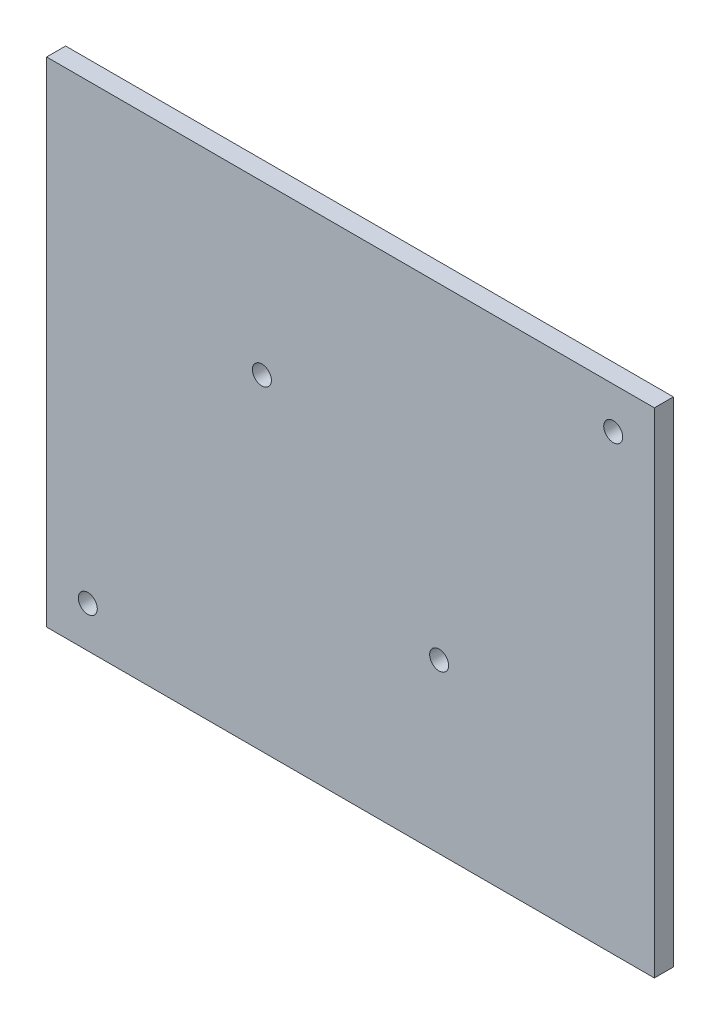
SolidWorks part; units mm, degrees
ref_plane "Alzado" through (0, 0, 0) normal (0, 0, 1) x (1, 0, 0)
ref_plane "Planta" through (0, 0, 0) normal (0, 1, 0) x (1, 0, 0)
ref_plane "Vista lateral" through (0, 0, 0) normal (1, 0, 0) x (0, 0, -1)
sketch "Croquis1" plane through (0, 0, 0) normal (0, 0, 1) x (1, 0, 0)
  line L5 (-48, -39) -> (48, -39)
  line L6 (-48, -39) -> (-48, 39)
  line L19 (-48, 39) -> (48, 39)
  line L24 (48, -39) -> (48, 39)
  line L25 (-48, -39) -> (48, 39) construction
  line L26 (-48, 39) -> (48, -39) construction
  point P0 (0, 0)
  dimension "D1" = 96
  dimension "D2" = 78
extrude "Saliente-Extruir2" add sketch "Croquis1" against normal blind 3 contours L5 region at (0, 0, 0)
sketch "Croquis2" plane through (0, 0, 0) normal (0, 0, 1) x (1, 0, 0)
  line L0 (0, 39) -> (0, -39) construction
  line L1 (-21.5, 20) -> (21.5, 20) construction
  line L2 (-21.5, 20) -> (-21.5, -20) construction
  line L3 (-21.5, -20) -> (21.5, -20) construction
  line L4 (21.5, 20) -> (21.5, -20) construction
  line L5 (-48, 39) -> (48, 39) construction
  line L6 (0, 20) -> (0, -20) construction
  line L15 (-21.5, 0) -> (21.5, 0) construction
  line L16 (-48, -39) -> (48, -39) construction
  line L17 (-48, 0) -> (48, 0) construction
  line L18 (-48, -39) -> (-48, 39) construction
  line L20 (-48, 39) -> (48, 39)
  line L21 (48, -39) -> (48, 39) construction
  line L22 (-48, 39) -> (-48, -39)
  line L23 (-48, -39) -> (48, -39)
  line L24 (48, 39) -> (48, -39)
  circle A1 centre (-14, 12.5) radius 1.5
  circle A2 centre (14, -12.5) radius 1.5
  circle A3 centre (-41.5, -32.5) radius 1.5 construction
  circle A4 centre (41.5, 32.5) radius 1.5 construction
  circle A5 centre (-41.5, -32.5) radius 1.5
  circle A6 centre (41.5, 32.5) radius 1.5
  point P8 (0, 0)
  dimension "D1" = 7.5
  dimension "D2" = 7.5
  dimension "D3" = 7.5
  dimension "D4" = 3
  dimension "D7" = 3
  dimension "D5" = 43
  dimension "D6" = 40
  dimension "D9" = 7.5
extrude "Cortar-Extruir1" cut sketch "Croquis2" against normal through all flip side to cut
sketch "Sketch6" plane through (0, 0, 0) normal (0, 0, 1) x (1, 0, 0)
  line L0 (1.7275, -9.1526) -> (1.7275, -16.0516)
  line L1 (2.8268, -16.0516) -> (2.8268, -9.1526)
  line L2 (2.2798, -8.9746) -> (2.2801, -8.9746)
  line L3 (-11.373, -9.3975) -> (-11.373, -16.0515)
  line L4 (-10.2742, -16.0515) -> (-10.2742, -12.9911)
  line L5 (-10.2742, -12.9911) -> (-9.54, -12.9911)
  line L6 (-7.8119, -14.3075) -> (-7.0556, -15.9986)
  line L7 (-6.0064, -15.6431) -> (-6.7462, -14.0625)
  line L8 (-9.2084, -9.0081) -> (-10.9645, -9.0083)
  line L9 (-4.2786, -9.3975) -> (-4.2786, -16.0515)
  line L10 (-3.1793, -16.0515) -> (-3.1793, -13.0584)
  line L11 (-3.1793, -13.0584) -> (-0.3195, -13.0584)
  line L12 (-0.3195, -12.2597) -> (-3.1793, -12.2597)
  line L13 (-3.1793, -12.2597) -> (-3.1793, -9.8191)
  line L14 (-3.1793, -9.8191) -> (-0.1539, -9.8191)
  line L15 (-0.1539, -9.0062) -> (-3.8702, -9.0083)
  line L16 (5.024, -9.3975) -> (5.024, -15.8065)
  line L17 (5.4325, -16.1957) -> (7.1771, -16.1957)
  line L18 (7.2987, -9.0086) -> (5.4325, -9.0083)
  line L19 (-10.2744, -9.7961) -> (-9.3524, -9.7961)
  line L20 (-9.2031, -12.2181) -> (-10.2742, -12.2181)
  line L21 (-10.2742, -12.2181) -> (-10.2744, -9.7961)
  line L22 (6.1171, -9.8011) -> (7.2378, -9.8011)
  line L23 (7.2489, -15.3934) -> (6.1171, -15.3934)
  line L24 (6.1171, -15.3934) -> (6.1171, -9.8011)
  line L25 (-11.5, -6.9036) -> (-11.5, 9.9857)
  line L26 (-11.5, 9.9857) -> (-5.3069, 16.2)
  line L27 (-5.3069, 16.2) -> (11.5, 16.2)
  line L28 (11.5, 16.2) -> (11.5, -7.0088)
  line L29 (11.5, -7.0088) -> (10.3931, -8.0105)
  line L30 (10.3931, -8.0105) -> (-10.4983, -8.0105)
  line L31 (-10.4983, -8.0105) -> (-11.5, -6.9036)
  line L32 (10.3297, -3.7737) -> (-8.4737, -3.7737)
  line L33 (-8.4737, -3.7737) -> (-8.4737, 8.8007)
  line L34 (-8.4737, 8.8007) -> (-4.0713, 13.1737)
  line L35 (-4.0713, 13.1737) -> (8.4737, 13.1737)
  line L36 (8.4737, 13.1737) -> (8.4737, -0.7474)
  line L37 (8.4737, -0.7474) -> (-5.4474, -0.7474)
  line L38 (-5.4474, -0.7474) -> (-5.4474, 7.6003)
  line L39 (-2.8521, 10.1474) -> (5.4474, 10.1474)
  line L40 (5.4474, 10.1474) -> (5.4474, 4.0947)
  line L41 (5.4474, 4.0947) -> (2.4211, 4.0947)
  line L42 (2.4211, 4.0947) -> (2.4211, 2.279)
  line L43 (2.4211, 2.279) -> (-2.4211, 2.279)
  line L44 (-2.4211, 2.279) -> (-2.4211, 7.1211)
  line L45 (-2.4211, 7.1211) -> (2.4211, 7.1211)
  line L46 (2.4211, 7.1211) -> (2.4211, 5.3053)
  line L47 (2.4211, 5.3053) -> (4.2369, 5.3053)
  line L48 (4.2369, 5.3053) -> (4.2369, 8.9368)
  line L49 (4.2369, 8.9368) -> (-1.9416, 8.9368)
  line L50 (-4.2368, 6.6956) -> (-4.2368, 0.4632)
  line L51 (-4.2368, 0.4632) -> (7.2632, 0.4632)
  line L52 (7.2632, 0.4632) -> (7.2632, 11.9632)
  line L53 (7.2632, 11.9632) -> (-3.1624, 11.9632)
  line L54 (-7.2631, 7.8939) -> (-7.2631, -2.5632)
  line L55 (-7.2631, -2.5632) -> (10.2895, -2.5632)
  line L56 (10.2895, -2.5632) -> (10.2895, 14.9895)
  line L57 (10.2895, 14.9895) -> (-4.3773, 14.9895)
  line L58 (-10.2895, 9.0995) -> (-10.2895, -5.186)
  line L59 (-10.2895, -5.186) -> (-9.8779, -5.5975)
  line L60 (-9.8779, -5.5975) -> (10.3297, -5.5975)
  line L61 (10.3297, -5.5975) -> (10.3297, -3.7737)
  line L62 (-5.3069, 16.2) -> (-11.5, 9.9857)
  line L63 (-1.9416, 8.9368) -> (-4.2368, 6.6956)
  line L64 (-2.8521, 10.1474) -> (-5.4474, 7.6003)
  line L65 (-3.1624, 11.9632) -> (-7.2631, 7.8939)
  line L66 (-4.3773, 14.9895) -> (-10.2895, 9.0995)
  spline S0 degree 3 poles (2.2801, -8.9746) (2.1823, -8.9746) (2.093, -8.977) (2.0206, -8.9893) knots 0 0 0 0 1 1 1 1
  spline S1 degree 3 poles (2.0206, -8.9893) (1.9525, -8.9967) (1.8962, -9.009) (1.8496, -9.023) knots 0 0 0 0 1 1 1 1
  spline S2 degree 3 poles (1.8496, -9.023) (1.8069, -9.0353) (1.7769, -9.0538) (1.7557, -9.0759) knots 0 0 0 0 1 1 1 1
  spline S3 degree 3 poles (1.7557, -9.0759) (1.7388, -9.098) (1.7275, -9.1231) (1.7275, -9.1526) knots 0 0 0 0 1 1 1 1
  spline S4 degree 3 poles (1.7275, -16.0516) (1.7275, -16.0811) (1.7388, -16.1062) (1.7557, -16.1284) knots 0 0 0 0 1 1 1 1
  spline S5 degree 3 poles (1.7557, -16.1284) (1.7727, -16.1505) (1.8015, -16.1712) (1.8439, -16.1859) knots 0 0 0 0 1 1 1 1
  spline S6 degree 3 poles (1.8439, -16.1859) (1.8863, -16.1982) (1.9429, -16.2031) (2.0149, -16.2105) knots 0 0 0 0 1 1 1 1
  spline S7 degree 3 poles (2.0149, -16.2105) (2.0873, -16.2228) (2.1778, -16.2302) (2.2798, -16.2302) knots 0 0 0 0 1 1 1 1
  spline S8 degree 3 poles (2.2798, -16.2302) (2.3861, -16.2302) (2.4712, -16.2228) (2.5393, -16.2105) knots 0 0 0 0 1 1 1 1
  spline S9 degree 3 poles (2.5393, -16.2105) (2.6117, -16.2031) (2.6679, -16.1982) (2.7103, -16.1859) knots 0 0 0 0 1 1 1 1
  spline S10 degree 3 poles (2.7103, -16.1859) (2.753, -16.1712) (2.7815, -16.1505) (2.7985, -16.1284) knots 0 0 0 0 1 1 1 1
  spline S11 degree 3 poles (2.7985, -16.1284) (2.8155, -16.1062) (2.8268, -16.0811) (2.8268, -16.0516) knots 0 0 0 0 1 1 1 1
  spline S12 degree 3 poles (2.8268, -9.1526) (2.8268, -9.1231) (2.8155, -9.098) (2.7985, -9.0759) knots 0 0 0 0 1 1 1 1
  spline S13 degree 3 poles (2.7985, -9.0759) (2.7815, -9.0538) (2.7527, -9.0341) (2.7103, -9.023) knots 0 0 0 0 1 1 1 1
  spline S14 degree 3 poles (2.7103, -9.023) (2.6676, -9.0083) (2.6114, -8.9967) (2.5393, -8.9893) knots 0 0 0 0 1 1 1 1
  spline S15 degree 3 poles (2.5393, -8.9893) (2.4712, -8.977) (2.3861, -8.9746) (2.2798, -8.9746) knots 0 0 0 0 1 1 1 1
  spline S16 degree 3 poles (-10.9645, -9.0083) (-11.0623, -9.0083) (-11.1567, -9.0356) (-11.2461, -9.0948) knots 0 0 0 0 1 1 1 1
  spline S17 degree 3 poles (-11.2461, -9.0948) (-11.3311, -9.1504) (-11.373, -9.253) (-11.373, -9.3975) knots 0 0 0 0 1 1 1 1
  spline S18 degree 3 poles (-11.373, -16.0515) (-11.373, -16.081) (-11.3673, -16.1061) (-11.3504, -16.1282) knots 0 0 0 0 1 1 1 1
  spline S19 degree 3 poles (-11.3504, -16.1282) (-11.3334, -16.1504) (-11.2992, -16.171) (-11.2565, -16.1858) knots 0 0 0 0 1 1 1 1
  spline S20 degree 3 poles (-11.2565, -16.1858) (-11.2138, -16.1981) (-11.159, -16.203) (-11.0909, -16.2104) knots 0 0 0 0 1 1 1 1
  spline S21 degree 3 poles (-11.0909, -16.2104) (-11.0185, -16.2227) (-10.9323, -16.2301) (-10.826, -16.2301) knots 0 0 0 0 1 1 1 1
  spline S22 degree 3 poles (-10.826, -16.2301) (-10.7197, -16.2301) (-10.629, -16.2227) (-10.5612, -16.2104) knots 0 0 0 0 1 1 1 1
  spline S23 degree 3 poles (-10.5612, -16.2104) (-10.4888, -16.203) (-10.4337, -16.1981) (-10.3955, -16.1858) knots 0 0 0 0 1 1 1 1
  spline S24 degree 3 poles (-10.3955, -16.1858) (-10.3528, -16.171) (-10.3243, -16.1504) (-10.3073, -16.1282) knots 0 0 0 0 1 1 1 1
  spline S25 degree 3 poles (-10.3073, -16.1282) (-10.2847, -16.1061) (-10.2742, -16.081) (-10.2742, -16.0515) knots 0 0 0 0 1 1 1 1
  spline S26 degree 3 poles (-9.54, -12.9911) (-9.2889, -12.9911) (-9.0782, -13.0253) (-8.8995, -13.092) knots 0 0 0 0 1 1 1 1
  spline S27 degree 3 poles (-8.8995, -13.092) (-8.7209, -13.155) (-8.5622, -13.2425) (-8.4303, -13.361) knots 0 0 0 0 1 1 1 1
  spline S28 degree 3 poles (-8.4303, -13.361) (-8.2982, -13.4759) (-8.1872, -13.6161) (-8.0935, -13.779) knots 0 0 0 0 1 1 1 1
  spline S29 degree 3 poles (-8.0935, -13.779) (-7.9957, -13.9382) (-7.9013, -14.1149) (-7.8119, -14.3075) knots 0 0 0 0 1 1 1 1
  spline S30 degree 3 poles (-7.0556, -15.9986) (-7.0386, -16.0431) (-7.016, -16.0795) (-6.9948, -16.1091) knots 0 0 0 0 1 1 1 1
  spline S31 degree 3 poles (-6.9948, -16.1091) (-6.9694, -16.1386) (-6.938, -16.1674) (-6.8953, -16.1858) knots 0 0 0 0 1 1 1 1
  spline S32 degree 3 poles (-6.8953, -16.1858) (-6.8529, -16.2006) (-6.7978, -16.2079) (-6.7297, -16.2146) knots 0 0 0 0 1 1 1 1
  spline S33 degree 3 poles (-6.7297, -16.2146) (-6.6573, -16.222) (-6.5643, -16.2293) (-6.4535, -16.2293) knots 0 0 0 0 1 1 1 1
  spline S34 degree 3 poles (-6.4535, -16.2293) (-6.326, -16.2293) (-6.2209, -16.222) (-6.1444, -16.2146) knots 0 0 0 0 1 1 1 1
  spline S35 degree 3 poles (-6.1444, -16.2146) (-6.0678, -16.2072) (-6.0104, -16.1998) (-5.9677, -16.1858) knots 0 0 0 0 1 1 1 1
  spline S36 degree 3 poles (-5.9677, -16.1858) (-5.9253, -16.171) (-5.8976, -16.1504) (-5.8849, -16.1282) knots 0 0 0 0 1 1 1 1
  spline S37 degree 3 poles (-5.8849, -16.1282) (-5.8707, -16.1061) (-5.8679, -16.081) (-5.8679, -16.0515) knots 0 0 0 0 1 1 1 1
  spline S38 degree 3 poles (-5.8679, -16.0515) (-5.8679, -16.022) (-5.8736, -15.9784) (-5.8905, -15.9265) knots 0 0 0 0 1 1 1 1
  spline S39 degree 3 poles (-5.8905, -15.9265) (-5.9075, -15.8709) (-5.9468, -15.7765) (-6.0064, -15.6431) knots 0 0 0 0 1 1 1 1
  spline S40 degree 3 poles (-6.7462, -14.0625) (-6.8313, -13.8809) (-6.915, -13.7168) (-7.0001, -13.5724) knots 0 0 0 0 1 1 1 1
  spline S41 degree 3 poles (-7.0001, -13.5724) (-7.0851, -13.428) (-7.1781, -13.2992) (-7.2762, -13.1881) knots 0 0 0 0 1 1 1 1
  spline S42 degree 3 poles (-7.2762, -13.1881) (-7.3698, -13.0769) (-7.4693, -12.9825) (-7.5799, -12.9046) knots 0 0 0 0 1 1 1 1
  spline S43 degree 3 poles (-7.5799, -12.9046) (-7.6904, -12.8232) (-7.8193, -12.7595) (-7.9553, -12.7076) knots 0 0 0 0 1 1 1 1
  spline S44 degree 3 poles (-7.9553, -12.7076) (-7.7128, -12.6336) (-7.4885, -12.5411) (-7.2928, -12.4337) knots 0 0 0 0 1 1 1 1
  spline S45 degree 3 poles (-7.2928, -12.4337) (-7.0972, -12.3263) (-6.9308, -12.2035) (-6.7904, -12.059) knots 0 0 0 0 1 1 1 1
  spline S46 degree 3 poles (-6.7904, -12.059) (-6.6499, -11.9109) (-6.5425, -11.7386) (-6.4702, -11.5497) knots 0 0 0 0 1 1 1 1
  spline S47 degree 3 poles (-6.4702, -11.5497) (-6.3936, -11.3571) (-6.3596, -11.1418) (-6.3596, -10.9012) knots 0 0 0 0 1 1 1 1
  spline S48 degree 3 poles (-6.3596, -10.9012) (-6.3596, -10.6531) (-6.4015, -10.4274) (-6.4866, -10.2238) knots 0 0 0 0 1 1 1 1
  spline S49 degree 3 poles (-6.4866, -10.2238) (-6.5674, -10.0164) (-6.6907, -9.8353) (-6.8565, -9.6761) knots 0 0 0 0 1 1 1 1
  spline S50 degree 3 poles (-6.8565, -9.6761) (-7.0224, -9.5169) (-7.228, -9.3858) (-7.4748, -9.2821) knots 0 0 0 0 1 1 1 1
  spline S51 degree 3 poles (-7.4748, -9.2821) (-7.7173, -9.1786) (-7.9949, -9.0996) (-8.314, -9.0516) knots 0 0 0 0 1 1 1 1
  spline S52 degree 3 poles (-8.314, -9.0516) (-8.4245, -9.0393) (-8.5545, -9.0295) (-8.6949, -9.0229) knots 0 0 0 0 1 1 1 1
  spline S53 degree 3 poles (-8.6949, -9.0229) (-8.8312, -9.0106) (-8.9999, -9.0081) (-9.2084, -9.0081) knots 0 0 0 0 1 1 1 1
  spline S54 degree 3 poles (-3.8702, -9.0083) (-3.968, -9.0083) (-4.0624, -9.0356) (-4.1517, -9.0948) knots 0 0 0 0 1 1 1 1
  spline S55 degree 3 poles (-4.1517, -9.0948) (-4.2368, -9.1504) (-4.2786, -9.253) (-4.2786, -9.3975) knots 0 0 0 0 1 1 1 1
  spline S56 degree 3 poles (-4.2786, -16.0515) (-4.2786, -16.0773) (-4.2673, -16.1024) (-4.2504, -16.1282) knots 0 0 0 0 1 1 1 1
  spline S57 degree 3 poles (-4.2504, -16.1282) (-4.2334, -16.1504) (-4.2046, -16.171) (-4.1622, -16.1858) knots 0 0 0 0 1 1 1 1
  spline S58 degree 3 poles (-4.1622, -16.1858) (-4.1198, -16.1981) (-4.0632, -16.203) (-3.9912, -16.2104) knots 0 0 0 0 1 1 1 1
  spline S59 degree 3 poles (-3.9912, -16.2104) (-3.9188, -16.2227) (-3.8283, -16.2301) (-3.7263, -16.2301) knots 0 0 0 0 1 1 1 1
  spline S60 degree 3 poles (-3.7263, -16.2301) (-3.6158, -16.2301) (-3.5293, -16.2227) (-3.4614, -16.2104) knots 0 0 0 0 1 1 1 1
  spline S61 degree 3 poles (-3.4614, -16.2104) (-3.3933, -16.203) (-3.3385, -16.1981) (-3.2958, -16.1858) knots 0 0 0 0 1 1 1 1
  spline S62 degree 3 poles (-3.2958, -16.1858) (-3.2531, -16.171) (-3.2189, -16.1504) (-3.2019, -16.1282) knots 0 0 0 0 1 1 1 1
  spline S63 degree 3 poles (-3.2019, -16.1282) (-3.185, -16.1024) (-3.1793, -16.0773) (-3.1793, -16.0515) knots 0 0 0 0 1 1 1 1
  spline S64 degree 3 poles (-0.3195, -13.0584) (-0.2898, -13.0584) (-0.2621, -13.0485) (-0.2367, -13.0338) knots 0 0 0 0 1 1 1 1
  spline S65 degree 3 poles (-0.2367, -13.0338) (-0.207, -13.0141) (-0.1807, -12.9912) (-0.1592, -12.9617) knots 0 0 0 0 1 1 1 1
  spline S66 degree 3 poles (-0.1592, -12.9617) (-0.1366, -12.9285) (-0.1236, -12.8896) (-0.1151, -12.8417) knots 0 0 0 0 1 1 1 1
  spline S67 degree 3 poles (-0.1151, -12.8417) (-0.1067, -12.7898) (-0.1038, -12.7246) (-0.1038, -12.6542) knots 0 0 0 0 1 1 1 1
  spline S68 degree 3 poles (-0.1038, -12.6542) (-0.1038, -12.5765) (-0.1064, -12.515) (-0.1151, -12.4668) knots 0 0 0 0 1 1 1 1
  spline S69 degree 3 poles (-0.1151, -12.4668) (-0.1236, -12.4149) (-0.1378, -12.3763) (-0.1592, -12.3468) knots 0 0 0 0 1 1 1 1
  spline S70 degree 3 poles (-0.1592, -12.3468) (-0.1819, -12.3172) (-0.2067, -12.2954) (-0.2367, -12.2843) knots 0 0 0 0 1 1 1 1
  spline S71 degree 3 poles (-0.2367, -12.2843) (-0.2621, -12.2695) (-0.2898, -12.2597) (-0.3195, -12.2597) knots 0 0 0 0 1 1 1 1
  spline S72 degree 3 poles (-0.1539, -9.8191) (-0.1242, -9.8191) (-0.0965, -9.8093) (-0.0711, -9.7945) knots 0 0 0 0 1 1 1 1
  spline S73 degree 3 poles (-0.0711, -9.7945) (-0.0414, -9.7798) (-0.0151, -9.7569) (0.0061, -9.7274) knots 0 0 0 0 1 1 1 1
  spline S74 degree 3 poles (0.0061, -9.7274) (0.0287, -9.6942) (0.0417, -9.6543) (0.0502, -9.6024) knots 0 0 0 0 1 1 1 1
  spline S75 degree 3 poles (0.0502, -9.6024) (0.0587, -9.5505) (0.0615, -9.4853) (0.0615, -9.415) knots 0 0 0 0 1 1 1 1
  spline S76 degree 3 poles (0.0615, -9.415) (0.0615, -9.3446) (0.059, -9.2844) (0.0502, -9.2325) knots 0 0 0 0 1 1 1 1
  spline S77 degree 3 poles (0.0502, -9.2325) (0.0417, -9.1769) (0.0276, -9.136) (0.0061, -9.1028) knots 0 0 0 0 1 1 1 1
  spline S78 degree 3 poles (0.0061, -9.1028) (-0.0165, -9.0694) (-0.0414, -9.0455) (-0.0711, -9.0308) knots 0 0 0 0 1 1 1 1
  spline S79 degree 3 poles (-0.0711, -9.0308) (-0.0965, -9.016) (-0.1242, -9.0062) (-0.1539, -9.0062) knots 0 0 0 0 1 1 1 1
  spline S80 degree 3 poles (5.4325, -9.0083) (5.3347, -9.0083) (5.2403, -9.0356) (5.151, -9.0948) knots 0 0 0 0 1 1 1 1
  spline S81 degree 3 poles (5.151, -9.0948) (5.0659, -9.1504) (5.024, -9.253) (5.024, -9.3975) knots 0 0 0 0 1 1 1 1
  spline S82 degree 3 poles (5.024, -15.8065) (5.024, -15.9508) (5.0659, -16.05) (5.151, -16.1091) knots 0 0 0 0 1 1 1 1
  spline S83 degree 3 poles (5.151, -16.1091) (5.2403, -16.1647) (5.3347, -16.1957) (5.4325, -16.1957) knots 0 0 0 0 1 1 1 1
  spline S84 degree 3 poles (7.1771, -16.1957) (7.8834, -16.1957) (8.4939, -16.117) (9.0045, -15.9652) knots 0 0 0 0 1 1 1 1
  spline S85 degree 3 poles (9.0045, -15.9652) (9.5151, -15.8135) (9.9475, -15.5866) (10.2964, -15.283) knots 0 0 0 0 1 1 1 1
  spline S86 degree 3 poles (10.2964, -15.283) (10.6495, -14.9757) (10.914, -14.5928) (11.0969, -14.13) knots 0 0 0 0 1 1 1 1
  spline S87 degree 3 poles (11.0969, -14.13) (11.2798, -13.6635) (11.3731, -13.1186) (11.3731, -12.4965) knots 0 0 0 0 1 1 1 1
  spline S88 degree 3 poles (11.3731, -12.4965) (11.3731, -11.956) (11.288, -11.4703) (11.1136, -11.0408) knots 0 0 0 0 1 1 1 1
  spline S89 degree 3 poles (11.1136, -11.0408) (10.9434, -10.6113) (10.6878, -10.2454) (10.3517, -9.9455) knots 0 0 0 0 1 1 1 1
  spline S90 degree 3 poles (10.3517, -9.9455) (10.0198, -9.6418) (9.6086, -9.4128) (9.1151, -9.2536) knots 0 0 0 0 1 1 1 1
  spline S91 degree 3 poles (9.1151, -9.2536) (8.6215, -9.0908) (8.0135, -9.0086) (7.2987, -9.0086) knots 0 0 0 0 1 1 1 1
  spline S92 degree 3 poles (-9.3524, -9.7961) (-9.1353, -9.7961) (-8.9598, -9.8035) (-8.8279, -9.8158) knots 0 0 0 0 1 1 1 1
  spline S93 degree 3 poles (-8.8279, -9.8158) (-8.6917, -9.8281) (-8.5699, -9.8426) (-8.4636, -9.8687) knots 0 0 0 0 1 1 1 1
  spline S94 degree 3 poles (-8.4636, -9.8687) (-8.1232, -9.9538) (-7.8795, -10.0953) (-7.7348, -10.2915) knots 0 0 0 0 1 1 1 1
  spline S95 degree 3 poles (-7.7348, -10.2915) (-7.5901, -10.4841) (-7.5194, -10.7211) (-7.5194, -11.0025) knots 0 0 0 0 1 1 1 1
  spline S96 degree 3 poles (-7.5194, -11.0025) (-7.5194, -11.1764) (-7.5508, -11.3396) (-7.6186, -11.4878) knots 0 0 0 0 1 1 1 1
  spline S97 degree 3 poles (-7.6186, -11.4878) (-7.6825, -11.6358) (-7.7874, -11.761) (-7.9278, -11.8721) knots 0 0 0 0 1 1 1 1
  spline S98 degree 3 poles (-7.9278, -11.8721) (-8.0683, -11.9793) (-8.2451, -12.0686) (-8.4578, -12.1315) knots 0 0 0 0 1 1 1 1
  spline S99 degree 3 poles (-8.4578, -12.1315) (-8.6664, -12.1908) (-8.9138, -12.2181) (-9.2031, -12.2181) knots 0 0 0 0 1 1 1 1
  spline S100 degree 3 poles (7.2378, -9.8011) (7.808, -9.8011) (8.273, -9.8707) (8.6346, -10.0077) knots 0 0 0 0 1 1 1 1
  spline S101 degree 3 poles (8.6346, -10.0077) (8.9963, -10.1447) (9.295, -10.335) (9.529, -10.5794) knots 0 0 0 0 1 1 1 1
  spline S102 degree 3 poles (9.529, -10.5794) (9.7673, -10.8239) (9.9428, -11.1168) (10.0535, -11.4538) knots 0 0 0 0 1 1 1 1
  spline S103 degree 3 poles (10.0535, -11.4538) (10.164, -11.787) (10.2191, -12.146) (10.2191, -12.5347) knots 0 0 0 0 1 1 1 1
  spline S104 degree 3 poles (10.2191, -12.5347) (10.2191, -13.0235) (10.1547, -13.4487) (10.0314, -13.8079) knots 0 0 0 0 1 1 1 1
  spline S105 degree 3 poles (10.0314, -13.8079) (9.9124, -14.1633) (9.7329, -14.4597) (9.4904, -14.6967) knots 0 0 0 0 1 1 1 1
  spline S106 degree 3 poles (9.4904, -14.6967) (9.2478, -14.9336) (8.9466, -15.1104) (8.585, -15.2252) knots 0 0 0 0 1 1 1 1
  spline S107 degree 3 poles (8.585, -15.2252) (8.2233, -15.34) (7.7765, -15.3934) (7.2489, -15.3934) knots 0 0 0 0 1 1 1 1
  spline S108 degree 3 poles (-5.4474, 7.6003) (-4.5823, 8.4493) (-3.7172, 9.2983) (-2.8521, 10.1474) knots 0 0 0 0 1 1 1 1
  spline S109 degree 3 poles (-1.9416, 8.9368) (-2.7067, 8.1898) (-3.4717, 7.4427) (-4.2368, 6.6956) knots 0 0 0 0 1 1 1 1
  spline S110 degree 3 poles (-3.1624, 11.9632) (-4.5293, 10.6067) (-5.8962, 9.2503) (-7.2631, 7.8939) knots 0 0 0 0 1 1 1 1
  spline S111 degree 2 poles (-4.3773, 14.9895) (-8.3188, 11.0628) (-10.2895, 9.0995) knots 0 0 0 1 1 1
